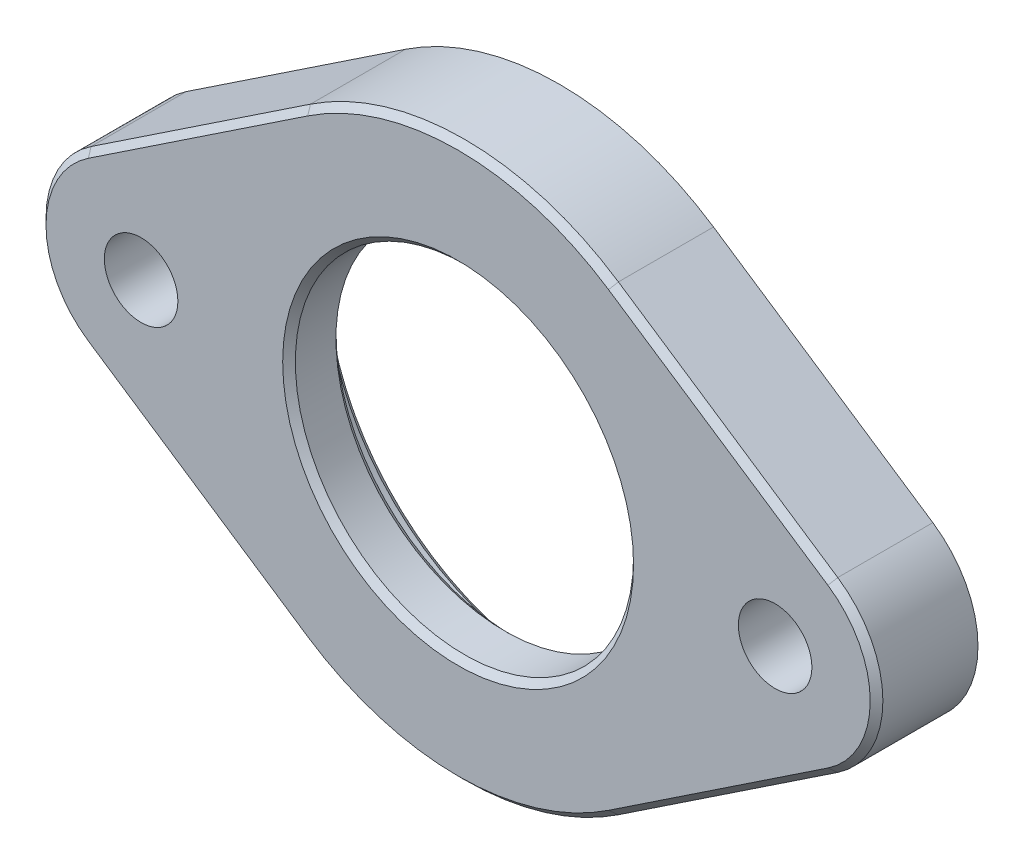
SolidWorks part; units mm, degrees
material "ABS"
ref_plane "Front Plane" through (0, 0, 0) normal (0, 0, 1) x (1, 0, 0)
ref_plane "Top Plane" through (0, 0, 0) normal (0, 1, 0) x (1, 0, 0)
ref_plane "Right Plane" through (0, 0, 0) normal (1, 0, 0) x (0, 0, -1)
sketch "Sketch1" plane through (0, 0, 0) normal (0, 0, 1) x (1, 0, 0)
  line L0 (-12.5, 0) -> (12.5, 0)
  line L1 (-6.0703, -9.0984) -> (-14.72, -3.3274)
  line L2 (-6.0703, 9.0984) -> (-14.72, 3.3274)
  line L3 (6.0703, 9.0984) -> (14.72, 3.3274)
  line L4 (6.0703, -9.0984) -> (14.72, -3.3274)
  circle A0 centre (0, 0) radius 6.6675
  circle A1 centre (0, 0) radius 8.9375
  circle A2 centre (0, 0) radius 10.9375
  circle A3 centre (-12.5, 0) radius 4
  circle A4 centre (12.5, 0) radius 4
  point P7 (0, 0)
  dimension "D1" = 13.335
  dimension "D2" = 17.875
  dimension "D4" = 8
  dimension "D3" = 2
  dimension "D5" = 25
extrude "Boss-Extrude1" add sketch "Sketch1" along normal blind 4 contours A3 L0 A2 L2 | A3 L1 A2 L0 | A3 | A4 L3 A2 L0 | A4 | A4 L0 A2 L4 | A2 region at (13.2988, 0, 0) region at (10.617, 5.2562, 0) region at (10.617, -5.2562, 0) region at (-10.617, 5.2562, 0) region at (-13.2988, 0, 0) region at (-10.617, -5.2562, 0)
extrude "Cut-Extrude1" cut sketch "Sketch1<4>" against normal through all both and the other way through all contours L0 A0 | L0 A0 region at (0, -2.8298, 0) region at (0, 2.8298, 0)
sketch "Sketch1<4>" plane through (0, 0, 0) normal (0, 0, 1) x (1, 0, 0) same geometry as "Sketch1"
extrude "Cut-Extrude2" cut sketch "Sketch1<6>" along normal blind 1.9 and the other way through all contours A1
sketch "Sketch1<6>" plane through (0, 0, 0) normal (0, 0, 1) x (1, 0, 0) same geometry as "Sketch1"
hole_wizard "M2.5 Clearance Hole1" positions "Sketch2" profile "Sketch3" hole size "M2.5" standard "ANSI Metric" end condition through all
sketch "Sketch2" plane through (0, 0, 4) normal (0, 0, 1) x (1, 0, 0)
  point P0 (-12.5, 0)
  point P3 (12.5, 0)
sketch "Sketch3" plane through (-12.5, 0, 4) normal (1, 0, 0) x (0, -1, 0)
  line L0 (0, 0) -> (0, 4)
  line L1 (0, 4) -> (1.45, 4)
  line L2 (1.45, 4) -> (1.45, 0)
  line L5 (1.45, 0) -> (0, 0)
  line L11 (0, -6.35) -> (0, 107.95) construction
  dimension "Thru Hole Dia." = 2.9
  dimension "Thru Hole Depth" = 4
chamfer "Chamfer1" distance 0.25 angle 45 12 edges at (6.6675, 0, 4) (6.6675, 0, 1.9) (8.9375, 0, 0) (8.9375, 0, 1.9) (10.3952, -6.2129, 4) (16.5, 0, 4) (0, -10.9375, 4) (10.3952, 6.2129, 4) (-10.3952, -6.2129, 4) (0, 10.9375, 4) (-16.5, 0, 4) (-10.3952, 6.2129, 4)
equation "\"D2@Sketch1\"=15.875mm+2"
